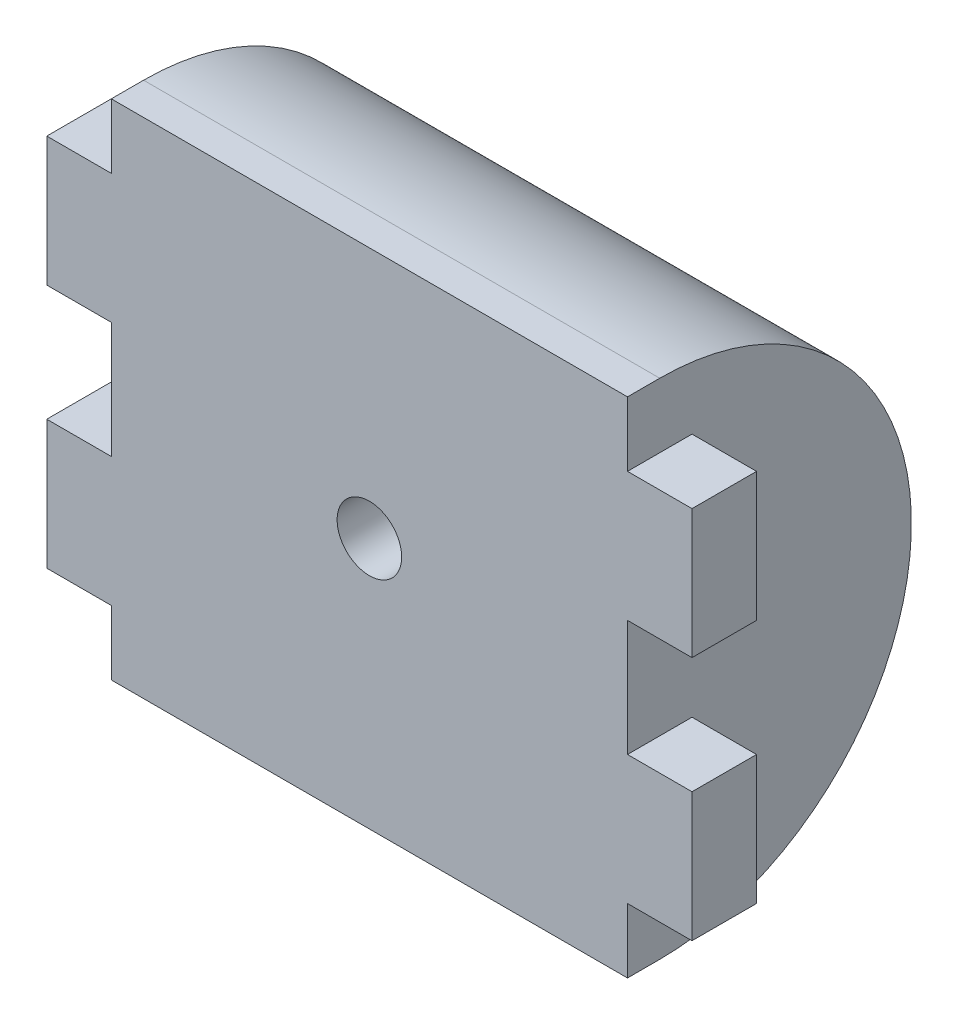
SolidWorks part; units mm, degrees
ref_plane "Front Plane" through (0, 0, 0) normal (0, 0, 1) x (1, 0, 0)
ref_plane "Top Plane" through (0, 0, 0) normal (0, 1, 0) x (1, 0, 0)
ref_plane "Right Plane" through (0, 0, 0) normal (1, 0, 0) x (0, 0, -1)
sketch "Sketch1" plane through (0, 0, 0) normal (0, 0, 1) x (1, 0, 0)
  line L0 (-25, 14.5) -> (-20, 14.5)
  line L1 (-20, -19.5) -> (20, -19.5)
  line L2 (-25, -14.5) -> (-25, -4.5)
  line L3 (-20, 19.5) -> (20, 19.5)
  line L4 (25, -14.5) -> (25, -4.5)
  line L5 (25, 14.5) -> (20, 14.5)
  line L7 (20, 4.5) -> (25, 4.5)
  line L8 (-20, 4.5) -> (-25, 4.5)
  line L9 (-25, -14.5) -> (-20, -14.5)
  line L10 (25, -4.5) -> (20, -4.5)
  line L11 (-20, -4.5) -> (-25, -4.5)
  line L12 (-20, 14.5) -> (-20, 19.5)
  line L13 (-20, 4.5) -> (-20, -4.5)
  line L14 (-25, 4.5) -> (-25, 14.5)
  line L15 (-20, -14.5) -> (-20, -19.5)
  line L17 (20, -14.5) -> (25, -14.5)
  line L18 (20, 14.5) -> (20, 19.5)
  line L19 (20, -14.5) -> (20, -19.5)
  line L20 (20, 4.5) -> (20, -4.5)
  line L21 (25, 4.5) -> (25, 14.5)
  circle A1 centre (0, 0) radius 2.5
  point P0 (0, 0)
  dimension "D3" = 5
  dimension "D5" = 5
  dimension "D1" = 10
  dimension "D2" = 10
  dimension "D4" = 5
  dimension "D6" = 10
  dimension "D7" = 5
  dimension "D8" = 10
  dimension "D9" = 5
  dimension "D10" = 5
  dimension "D11" = 5
  dimension "D12" = 9
  dimension "D13" = 9
  dimension "D14" = 40
  dimension "D15" = 40
extrude "Boss-Extrude1" add sketch "Sketch1" along normal blind 5
sketch "Sketch39" plane through (0, 0, 0) normal (0, 0, -1) x (-1, 0, 0)
  line L1 (-20, -19.5) -> (20, -19.5)
  line L2 (-20, -19.5) -> (-20, 19.5)
  line L3 (-20, 19.5) -> (20, 19.5)
  line L4 (20, -19.5) -> (20, 19.5)
  line L5 (-20, -19.5) -> (20, 19.5) construction
  line L6 (-20, 19.5) -> (20, -19.5) construction
  circle A0 centre (0, 0) radius 10
extrude "Boss-Extrude13" add sketch "Sketch39" along normal blind 17
sketch "Sketch40" plane through (20, 0, 0) normal (1, 0, 0) x (0, 0, -1)
  line L0 (17, 19.5) -> (17, -19.5) construction
  line L5 (-2.5, 19.5) -> (-2.5, -19.5)
  line L6 (-5, 19.5) -> (17, 19.5)
  line L7 (-5, 19.5) -> (-5, -19.5)
  line L8 (-5, -19.5) -> (17, -19.5)
  line L9 (17, 19.5) -> (17, -19.5)
  arc A0 (-2.5, -19.5) -> (-2.5, 19.5) centre (-2.5, 0) ccw
  line M5 (-5, -19.5) -> (17, -19.5)
  line M6 (17, -19.5) -> (17, 19.5)
  line M7 (17, 19.5) -> (-5, 19.5)
extrude "Cut-Extrude10" cut sketch "Sketch40" against normal blind 57 contours A0 L9 M7 | A0 M5 M6 region at (20, 15.1443, -12.6443) region at (20, -15.1443, -12.6443)
sketch "Sketch41" plane through (0, 0, 0) normal (0, 0, -1) x (-1, 0, 0)
  circle A0 centre (0, 0) radius 2.3
  circle A1 centre (0, 0) radius 10
extrude "Boss-Extrude14" add sketch "Sketch41" along normal blind 3
